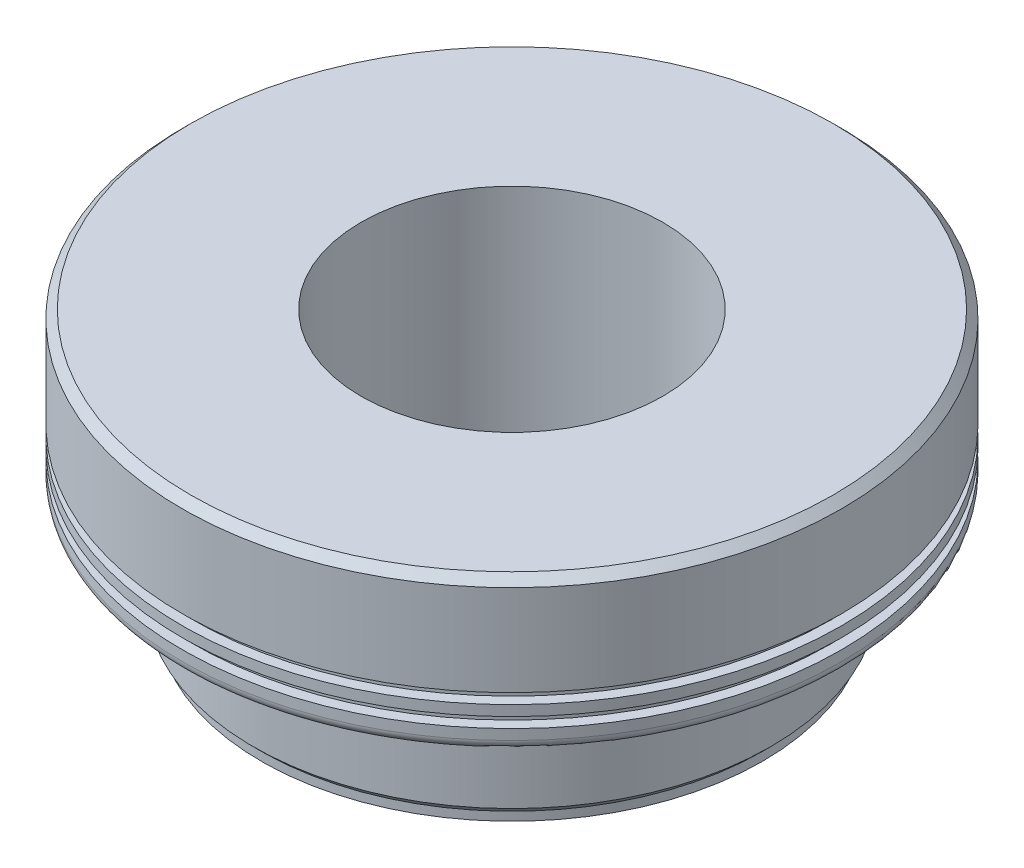
SolidWorks part; units mm, degrees
ref_plane "Front Plane" through (0, 0, 0) normal (0, 0, 1) x (1, 0, 0)
ref_plane "Top Plane" through (0, 0, 0) normal (0, 1, 0) x (1, 0, 0)
ref_plane "Right Plane" through (0, 0, 0) normal (1, 0, 0) x (0, 0, -1)
sketch "Sketch1" plane through (0, 0, 0) normal (0, 0, 1) x (1, 0, 0)
  line L0 (0, -1.765) -> (0, 1.765) construction
  line L1 (-4.37, 1.765) -> (4.37, 1.765) construction
  line L2 (-3.43, -1.765) -> (3.43, -1.765) construction
  line L3 (-2.0758, 1.7212) -> (-2.0758, 2.4212) construction
  line L4 (-2.0758, 2.4212) -> (-1.4696, 2.0712) construction
  line L5 (-1.4696, 2.0712) -> (-2.0758, 1.7212) construction
  line L6 (-2.0758, 2.0712) -> (-2, 2.0712) construction
  line L7 (-2, 2.0712) -> (-1.5453, 2.0712) construction
  line L8 (-1.5453, 2.0712) -> (-1.4696, 2.0712) construction
  line L9 (-1.5453, 2.0275) -> (-1.5453, 2.115) construction
  line L10 (-2, 1.765) -> (-2, 2.3775) construction
  line L11 (-2.0379, 1.7431) -> (-2.0379, 2.3994) construction
  point P4 (0, 0)
  point P7 (0, 1.765)
  point P10 (0, -0.235)
  point P13 (0, -1.765)
  point P14 (-2, 1.765)
  point P15 (2, 1.765)
  point P24 (-1.5453, 2.0712)
  point P28 (-2, 2.0712)
  point P31 (-2.0379, 2.0712)
  dimension "Head OD" = 8.74
  dimension "Head Height" = 2
  dimension "For Minimum Panel Thickness" = 1.53
  dimension "OD2" = 6.86
  dimension "Thread Pitch" = 0.7
  dimension "D1" = 0.0875
  dimension "Thread Size" = 4
sketch "Sketch2" plane through (0, 0, 0) normal (0, 0, 1) x (1, 0, 0)
  line L0 (0, -1.765) -> (0, 1.765) construction
  line L1 (-3.2, -1.765) -> (3.2, -1.765) construction
  line L2 (-3.2, -1.765) -> (-3.2, -0.235)
  line L3 (-3.2, -0.235) -> (3.2, -0.235) construction
  line L4 (3.2, -1.765) -> (3.2, -0.235)
  line L5 (-3.2, -1.765) -> (3.2, -0.235) construction
  line L6 (-3.2, -0.235) -> (3.2, -1.765) construction
  line L7 (-3.43, -1.765) -> (3.43, -1.765) construction
  point P0 (0, -1)
  dimension "Drill Bit Decimal Size Equivalent" = 6.4
sketch "Sketch3" plane through (0, 0, 0) normal (0, 0, 1) x (1, 0, 0)
  line L1 (-2, 1.765) -> (-2, -1.765)
  line L3 (-3.43, -1.765) -> (3.43, -1.765) construction
  line L4 (-4.37, 1.765) -> (4.37, 1.765) construction
  line L5 (-3.43, -1.5432) -> (-3.3229, -1.6503)
  line L6 (-3.3229, -1.6503) -> (-3.3229, -1.765)
  line L7 (-3.3229, -1.765) -> (-2, -1.765)
  line L8 (-2, 1.765) -> (-4.2629, 1.765)
  line L9 (-4.2629, 1.765) -> (-4.37, 1.6579)
  line L10 (-4.37, 1.6579) -> (-4.37, 0.4525)
  line L11 (-3.43, -1.5432) -> (-3.43, -0.5219) construction
  line L12 (-3.43, -0.5219) -> (-3.2, -0.5219) construction
  line L13 (-3.2, -0.235) -> (3.2, -0.235) construction
  line L14 (-3.2, -1.765) -> (-3.2, -0.235) construction
  line L15 (-3.2, -0.4143) -> (-3.2, -0.3426)
  line L16 (-3.3076, -0.235) -> (-4.2325, -0.235)
  line L17 (-4.37, 0.04) -> (-4.2325, 0.04)
  line L18 (-4.2325, 0.04) -> (-4.2325, 0.1775)
  line L19 (-4.2325, 0.1775) -> (-4.37, 0.1775)
  line L20 (-4.37, 0.315) -> (-4.2325, 0.315)
  line L21 (-4.2325, 0.315) -> (-4.2325, 0.4525)
  line L22 (-4.2325, 0.4525) -> (-4.37, 0.4525)
  line L23 (-4.37, 0.04) -> (-4.37, -0.0975)
  line L24 (-4.37, 0.315) -> (-4.37, 0.1775)
  line L25 (0, -1.765) -> (0, 1.765) construction
  line L26 (0, -1.765) -> (0, 1.765) construction
  line L27 (-3.43, -0.629) -> (-3.3229, -0.5219)
  line L28 (-3.43, -1.5432) -> (-3.43, -0.629)
  line L29 (-3.3229, -0.5219) -> (-3.3076, -0.5219)
  line L30 (3.43, -1.5432) -> (-3.43, -1.5432) construction
  arc A0 (-4.2325, -0.235) -> (-4.37, -0.0975) centre (-4.2325, -0.0975) cw
  arc A1 (-3.3076, -0.5219) -> (-3.2, -0.4143) centre (-3.3076, -0.4143) ccw
  arc A2 (-3.2, -0.3426) -> (-3.3076, -0.235) centre (-3.3076, -0.3426) ccw
  point P44 (-3.2, -0.235)
  point P46 (0, -1.5432)
  dimension "D4" = 0.1375
  dimension "D1" = 0.1076
  dimension "D2" = 45
  dimension "D3" = 0.2869
  dimension "D5" = 0.1375
  dimension "D6" = 3.43
  dimension "D7" = 0.2218
  dimension "D8" = 0.1147
  dimension "D9" = 0.1071
revolve "Revolve1" add sketch "Sketch3" angle 360 about L26
sketch "Sketch8" plane through (0, 0, 0) normal (0, 0, 1) x (1, 0, 0)
  line L0 (2, -1.765) -> (2, 1.765) construction
  line L1 (-2, 1.765) -> (-2, -1.765) construction
  line L2 (2, -1.765) -> (2, 1.765)
  line L3 (-2, 1.765) -> (-2, -1.765)
  line L4 (3.43, -1.5431) -> (3.43, -0.629) construction
  line L5 (-3.43, -0.629) -> (-3.43, -1.5432) construction
  line L6 (3.43, -1.5431) -> (3.43, -0.629)
  line L7 (-3.43, -0.629) -> (-3.43, -1.5432)
  point P4 (2, 0.715)
  dimension "D1" = 1.05
sketch "Sketch4" [suppressed] plane through (0, 1.765, 0) normal (0, 1, 0) x (1, 0, 0)
  circle A0 centre (0, 0) radius 2
curve "Helix/Spiral1" [suppressed] pitch 0.7 height 4.23 turns 6.0429
sketch "Sketch5" [suppressed] plane through (0, 0, 0) normal (0, 0, 1) x (1, 0, 0)
  line L0 (-2.0379, 1.7431) -> (-2.0379, 2.3994)
  line L1 (-2.0379, 2.3994) -> (-1.5453, 2.115)
  line L2 (-1.5453, 2.115) -> (-1.5453, 2.0275)
  line L3 (-1.5453, 2.0275) -> (-2.0379, 1.7431)
sweep "Sweep1" [suppressed] add profiles "Sketch5" path "Helix/Spiral1"
sketch "Sketch6" [suppressed] plane through (0, 0, 0) normal (0, 0, 1) x (1, 0, 0)
  line L1 (-2.0758, 2.7387) -> (-2.0758, 1.765)
  line L4 (-1.4696, 1.2346) -> (-1.4696, 2.7387)
  line L5 (-1.4696, 2.7387) -> (-2.0758, 2.7387)
  line L6 (-2.0758, -1.765) -> (-2, -1.765)
  line L7 (0, 0) -> (-4.37, 0) construction
  line L13 (0, -1.765) -> (0, 1.765) construction
  line L14 (0, -1.765) -> (0, 1.765) construction
  line L15 (-4.37, 1.6579) -> (-4.37, 0.4525) construction
  line L21 (-2, 1.765) -> (-1.4696, 1.2346)
  line L26 (-4.37, 1.765) -> (4.37, 1.765) construction
  line L27 (-2.0758, 1.765) -> (-2, 1.765)
  line L28 (-2.0758, 1.7212) -> (-2.0758, 2.4212) construction
  line L34 (-2, -1.765) -> (-1.4696, -1.2346)
  line L35 (-1.4696, -2.7387) -> (-2.0758, -2.7388)
  line L36 (-1.4696, -1.2346) -> (-1.4696, -2.7387)
  line L37 (-2.0758, -2.7388) -> (-2.0758, -1.765)
  point P16 (0, 0)
  dimension "D1" = 45
  dimension "D2" = 0.3175
  dimension "D3" = 45
revolve "Cut-Revolve1" [suppressed] cut sketch "Sketch6" angle 360 about L14
sketch "Sketch7" [suppressed] plane through (0, -1.765, 0) normal (0, -1, 0) x (1, 0, 0)
  line L1 (0, 0) -> (0, 3.2837) construction
  line L2 (-0.1071, 3.4692) -> (0.1071, 3.4692) construction
  line L3 (0.1071, 3.4692) -> (0, 3.2837) construction
  line L4 (0, 3.2837) -> (-0.1071, 3.4692) construction
  line L5 (0, 3.4692) -> (0, 3.43) construction
  line L6 (0, 3.43) -> (0, 3.3229) construction
  line L7 (0, 3.3229) -> (0, 3.2837) construction
  line L8 (-0.0226, 3.3229) -> (0.0226, 3.3229) construction
  line L9 (-0.0845, 3.43) -> (0.0845, 3.43)
  line L10 (0, 0) -> (0.0845, 3.43) construction
  line L12 (0.0226, 3.3228) -> (0.0845, 3.43)
  line L13 (-0.0845, 3.43) -> (-0.0226, 3.3228)
  line L14 (-0.0845, 3.43) -> (0, 0) construction
  circle A0 centre (0, 0) radius 3.3229 construction
  circle A1 centre (0, 0) radius 3.43 construction
  arc A2 (0.0226, 3.3228) -> (-0.0226, 3.3228) centre (0, 0) ccw
  circle A4 centre (0, 0) radius 3.3229 construction
  point P17 (0, 3.3229)
  point P21 (0, 3.43)
  dimension "D1" = 0.2142
  dimension "D2" = 0.0453
  dimension "D3" = 2.821
extrude "Cut-Extrude1" [suppressed] cut sketch "Sketch7" against normal up to vertex
fillet "Fillet1" [suppressed] radius 0.0113 tangent propagation no
fillet "Fillet2" [suppressed] radius 0.0113
fillet "Fillet3" [suppressed] radius 0.0113
pattern_circular "CirPattern2" [suppressed] count 95 over 360 of bodies 107
equation "\"D1@Sketch1\"=\"Thread Pitch@Sketch1\"/8"
equation "\"D3@Sketch3\"=\"For Minimum Panel Thickness@Sketch1\"*(3/16)"
equation "\"D4@Sketch3\"=\"Head Height@Sketch1\"*(11/160)"
equation "\"D5@Sketch3\"=\"D4@Sketch3\""
equation "\"D7@Sketch3\"=\"For Minimum Panel Thickness@Sketch1\"*0.145"
equation "\"D8@Sketch3\"=\"For Minimum Panel Thickness@Sketch1\"*0.075"
equation "\"D3@Helix/Spiral1\"=\"Head Height@Sketch1\"+\"For Minimum Panel Thickness@Sketch1\"+\"Thread Pitch@Sketch1\""
equation "\"D4@Helix/Spiral1\"=\"Thread Pitch@Sketch1\""
equation "\"D1@Sketch3\"=\"D3@Sketch3\"*0.375"
equation "\"D1@Sketch7\"=\"D9@Sketch3\"*2"
equation "\"D1@CirPattern2\"=int((360/\"D3@Sketch7\")*0.75)"
equation "\"D1@Fillet1\"=\"D2@Sketch7\"*0.25"
equation "\"D1@Fillet2\"=\"D1@Fillet1\""
equation "\"D1@Sketch8\"=\"Thread Pitch@Sketch1\"*1.5"
